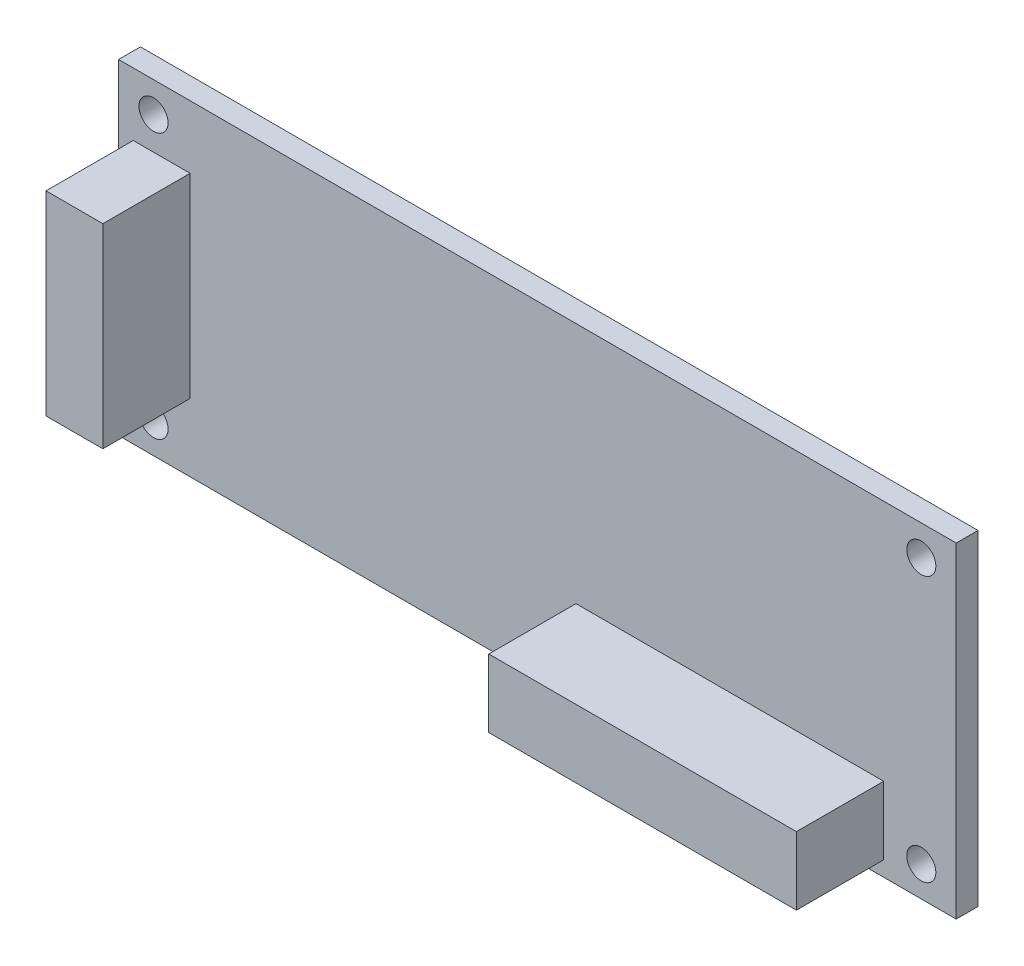
SolidWorks part; units mm, degrees
ref_plane "Front Plane" through (0, 0, 0) normal (0, 0, 1) x (1, 0, 0)
ref_plane "Top Plane" through (0, 0, 0) normal (0, 1, 0) x (1, 0, 0)
ref_plane "Right Plane" through (0, 0, 0) normal (1, 0, 0) x (0, 0, -1)
sketch "Sketch1" plane through (0, 0, 0) normal (0, 0, 1) x (1, 0, 0)
  line L1 (-45.72, -17.78) -> (45.72, -17.78)
  line L2 (-45.72, -17.78) -> (-45.72, 17.78)
  line L3 (-45.72, 17.78) -> (45.72, 17.78)
  line L4 (45.72, -17.78) -> (45.72, 17.78)
  line L5 (-45.72, -17.78) -> (45.72, 17.78) construction
  line L6 (-45.72, 17.78) -> (45.72, -17.78) construction
  point P0 (0, 0)
  dimension "D1" = 91.44
  dimension "D2" = 35.56
extrude "Boss-Extrude1" add sketch "Sketch1" along normal blind 2.3813
sketch "Sketch2" plane through (0, 0, 2.3813) normal (0, 0, 1) x (1, 0, 0)
  line L0 (-45.72, 17.78) -> (-45.72, -17.78) construction
  line L1 (45.72, 17.78) -> (-45.72, 17.78) construction
  circle A0 centre (-41.91, 14.478) radius 1.5875
  dimension "D1" = 3.175
  dimension "D2" = 3.81
  dimension "D3" = 3.302
extrude "Cut-Extrude1" cut sketch "Sketch2" against normal through all
mirror "Mirror1" about plane through (0, 0, 0) normal (1, 0, 0) of "Cut-Extrude1"
mirror "Mirror2" about plane through (0, 0, 0) normal (0, 1, 0) of "Mirror1"
sketch "Sketch3" plane through (0, 0, 2.3813) normal (0, 0, 1) x (1, 0, 0)
  line L1 (-44.1229, 10.9199) -> (-37.9147, 10.9199)
  line L2 (-44.1229, 10.9199) -> (-44.1229, -10.3656)
  line L3 (-44.1229, -10.3656) -> (-37.9147, -10.3656)
  line L4 (-37.9147, 10.9199) -> (-37.9147, -10.3656)
  line L5 (37.8038, -16.1304) -> (4.2127, -16.1304)
  line L6 (37.8038, -16.1304) -> (37.8038, -8.7026)
  line L7 (37.8038, -8.7026) -> (4.2127, -8.7026)
  line L8 (4.2127, -16.1304) -> (4.2127, -8.7026)
extrude "Boss-Extrude2" add sketch "Sketch3" along normal blind 9.525
